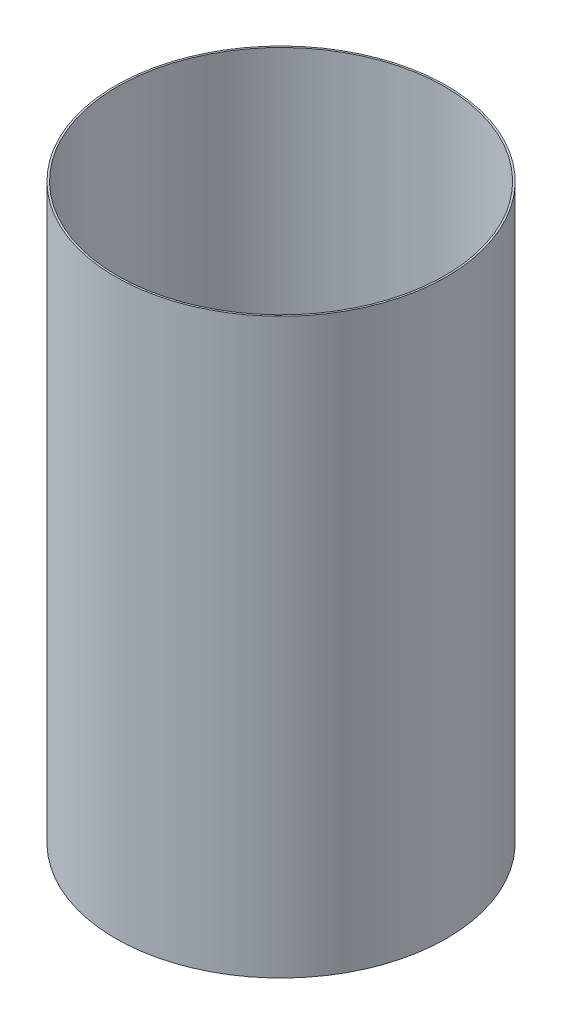
SolidWorks part; units mm, degrees
material "Glass"
ref_plane "Front Plane" through (0, 0, 0) normal (0, 0, 1) x (1, 0, 0)
ref_plane "Top Plane" through (0, 0, 0) normal (0, 1, 0) x (1, 0, 0)
ref_plane "Right Plane" through (0, 0, 0) normal (1, 0, 0) x (0, 0, -1)
sketch "Sketch1" plane through (0, 0, 0) normal (0, 1, 0) x (1, 0, 0)
  circle A0 centre (0, 0) radius 50.8
  dimension "D1" = 101.6
extrude "Extrude-Thin1" add sketch "Sketch1" along normal blind 177.8 thin thin type one direction wall 0.5588
